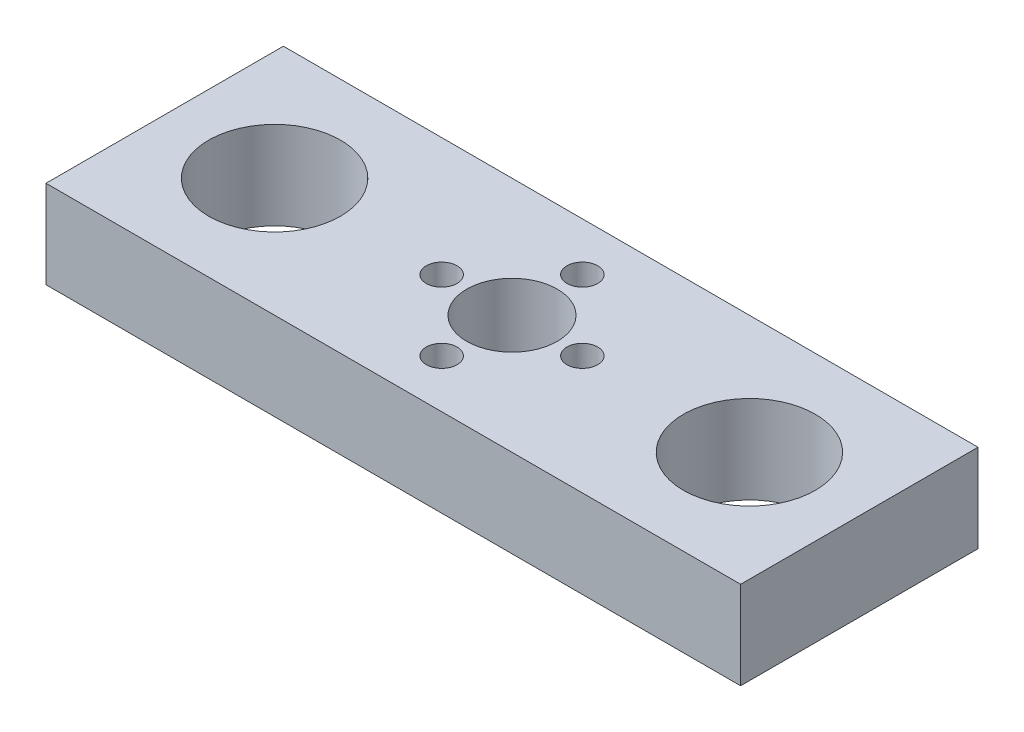
SolidWorks part; units mm, degrees
ref_plane "前视基准面" through (0, 0, 0) normal (0, 0, 1) x (1, 0, 0)
ref_plane "上视基准面" through (0, 0, 0) normal (0, 1, 0) x (1, 0, 0)
ref_plane "右视基准面" through (0, 0, 0) normal (1, 0, 0) x (0, 0, -1)
sketch "草图1" plane through (0, 0, 0) normal (0, 1, 0) x (1, 0, 0)
  line L1 (-39.5, 13.5) -> (39.5, 13.5)
  line L2 (-39.5, 13.5) -> (-39.5, -13.5)
  line L3 (-39.5, -13.5) -> (39.5, -13.5)
  line L4 (39.5, 13.5) -> (39.5, -13.5)
  line L5 (-39.5, 13.5) -> (39.5, -13.5) construction
  line L6 (-39.5, -13.5) -> (39.5, 13.5) construction
  point P0 (0, 0)
  dimension "D1" = 79
  dimension "D2" = 27
extrude "凸台-拉伸1" add sketch "草图1" along normal blind 10
sketch "草图2" plane through (0, 0, 0) normal (0, -1, 0) x (1, 0, 0)
  line L0 (-39.5, 0) -> (39.5, 0) construction
  line L1 (-39.5, -13.5) -> (-39.5, 13.5) construction
  line L2 (39.5, 13.5) -> (39.5, -13.5) construction
ref_plane "基准面1" through (0, 0, 0) normal (0, 0, 1) x (1, 0, 0)
sketch "草图3" plane through (0, 10, 0) normal (0, 1, 0) x (1, 0, 0)
  line L0 (-14.85, 0) -> (14.85, 0) construction
  line L1 (0, 13.5) -> (0, -13.5) construction
  line L2 (39.5, 13.5) -> (-39.5, 13.5) construction
  line L3 (-39.5, -13.5) -> (39.5, -13.5) construction
  circle A0 centre (-27, 0) radius 7.5
  circle A1 centre (27, 0) radius 7.5
  dimension "D1" = 15
  dimension "D2" = 54
extrude "切除-拉伸1" cut sketch "草图3" against normal through all contours A1 | A0
sketch "草图4" plane through (0, 10, 0) normal (0, 1, 0) x (1, 0, 0)
  line L0 (-39.5, 0) -> (39.5, 0) construction
  circle A0 centre (0, 0) radius 5.15
  point P3 (0, 0)
  point P4 (1.0884, 1.754)
  point P5 (0, 0)
  dimension "D1" = 10.3
extrude "切除-拉伸2" cut sketch "草图4" against normal through all
sketch "草图5" plane through (0, 10, 0) normal (0, 1, 0) x (1, 0, 0)
  circle A4 centre (8, 0) radius 1.75
  circle A8 centre (-8, 0) radius 1.75
  circle A9 centre (0, 8) radius 1.75
  circle A10 centre (0, -8) radius 1.75
  dimension "D1" = 3.5
extrude "切除-拉伸3" cut sketch "草图5" against normal through all
ref_plane "基准面2" through (0, 5, 0) normal (0, 1, 0) x (1, 0, 0)
sketch "草图6" plane through (0, 5, 0) normal (0, 1, 0) x (1, 0, 0)
  line L0 (-39.5, 9.5) -> (39.5, 9.5) construction
  line L1 (-39.5, 13.5) -> (-39.5, -13.5) construction
  line L2 (39.5, -13.5) -> (39.5, 13.5) construction
  line L3 (-39.5, -9.5) -> (39.5, -9.5) construction
  line L4 (-39.5, -13.5) -> (39.5, -13.5) construction
  line L5 (39.5, 13.5) -> (-39.5, 13.5) construction
  dimension "D1" = 4
  dimension "D2" = 4
